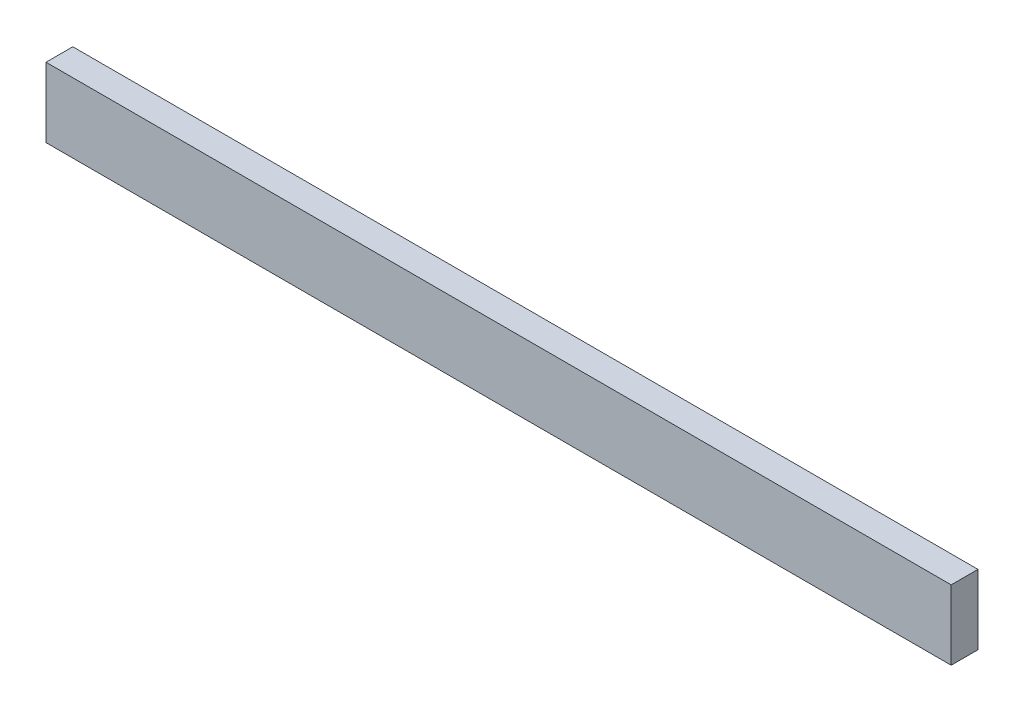
SolidWorks part; units mm, degrees
ref_plane "Front Plane" through (0, 0, 0) normal (0, 0, 1) x (1, 0, 0)
ref_plane "Top Plane" through (0, 0, 0) normal (0, 1, 0) x (1, 0, 0)
ref_plane "Right Plane" through (0, 0, 0) normal (1, 0, 0) x (0, 0, -1)
sketch "Sketch1" plane through (0, 0, 0) normal (0, 0, 1) x (1, 0, 0)
  line L1 (65, -5) -> (-65, -5)
  line L2 (65, -5) -> (65, 5)
  line L3 (65, 5) -> (-65, 5)
  line L4 (-65, -5) -> (-65, 5)
  line L5 (65, -5) -> (-65, 5) construction
  line L6 (65, 5) -> (-65, -5) construction
  point P0 (0, 0)
  dimension "D1" = 130
  dimension "D2" = 10
extrude "Boss-Extrude1" add sketch "Sketch1" along normal blind 3.85
